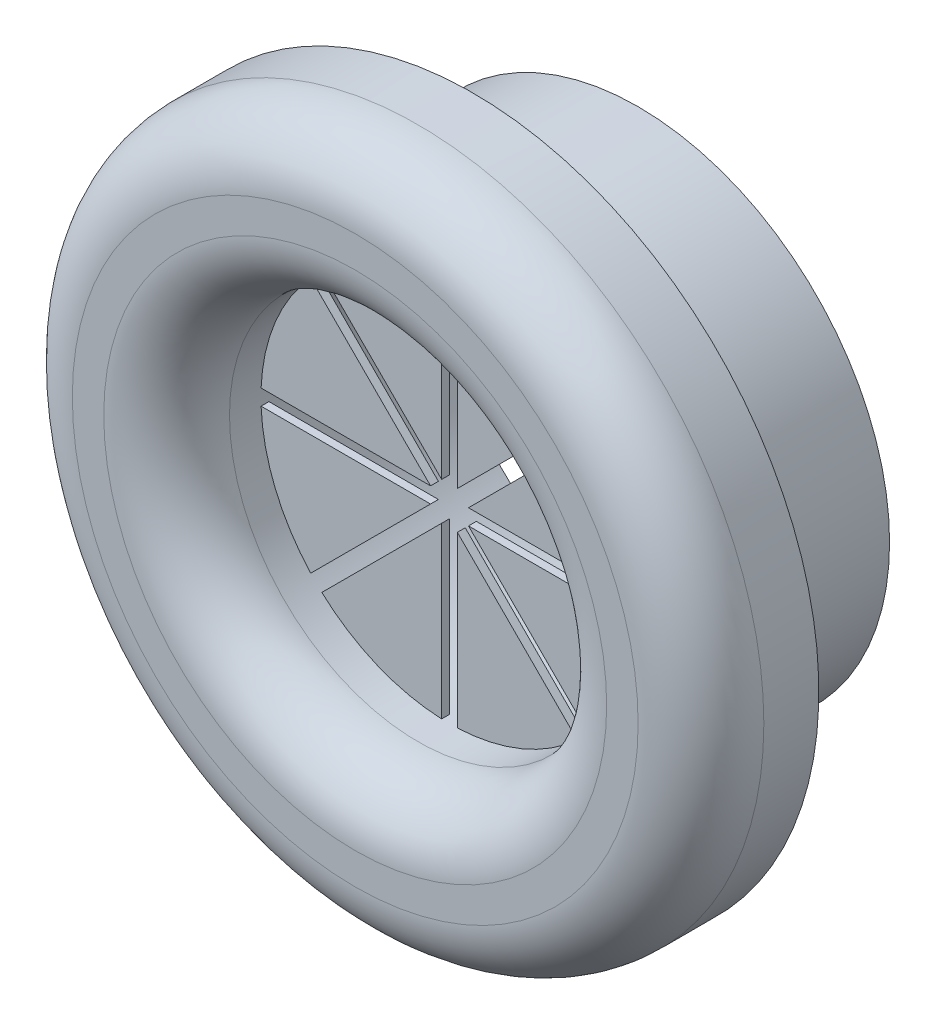
SolidWorks part; units mm, degrees
ref_plane "Płaszczyzna przednia" through (0, 0, 0) normal (0, 0, 1) x (1, 0, 0)
ref_plane "Płaszczyzna górna" through (0, 0, 0) normal (0, 1, 0) x (1, 0, 0)
ref_plane "Płaszczyzna prawa" through (0, 0, 0) normal (1, 0, 0) x (0, 0, -1)
sketch "Szkic1" plane through (0, 0, 0) normal (0, 0, 1) x (1, 0, 0)
  circle A0 centre (0, 0) radius 8
extrude "Dodanie-wyciągnięcie1" add sketch "Szkic1" along normal blind 5
sketch "Szkic2" plane through (0, 0, 5) normal (0, 0, 1) x (1, 0, 0)
  circle A0 centre (0, 0) radius 11
extrude "Dodanie-wyciągnięcie2" add sketch "Szkic2" along normal blind 4
sketch "Szkic3" plane through (0, 0, 9) normal (0, 0, 1) x (1, 0, 0)
  circle A0 centre (0, 0) radius 6
extrude "Wytnij-wyciągnięcie1" cut sketch "Szkic3" against normal through all
fillet "Zaokrąglenie1" radius 2 2 edges at (6, 0, 9) (11, 0, 9)
ref_plane "Płaszczyzna1" through (0, 0, 6) normal (0, 0, -1) x (-1, 0, 0)
sketch "Szkic4" plane through (0, 0, 6) normal (0, 0, -1) x (-1, 0, 0)
  line L0 (4.4157, -4.0622) -> (0.6036, -0.25)
  line L9 (5.9948, -0.25) -> (0.6036, -0.25) construction
  line L11 (0.6036, -0.25) -> (5.9948, -0.25)
  arc A1 (4.4157, -4.0622) -> (5.9948, -0.25) centre (0, 0) ccw
extrude "Dodanie-wyciągnięcie3" add sketch "Szkic4" along normal blind 0.25 contours L11 A1 L0
pattern_circular "Szyk kołowy1" count 8 over 360 about axis through (0, 0, 7) along (0, 0, 1) of "Dodanie-wyciągnięcie3"
sketch "Szkic5" plane through (0, 0, 5) normal (0, 0, -1) x (-1, 0, 0)
  circle A0 centre (0, 0) radius 10
  circle A1 centre (0, 0) radius 11
extrude "Wytnij-wyciągnięcie2" cut sketch "Szkic5" against normal blind 0.25
